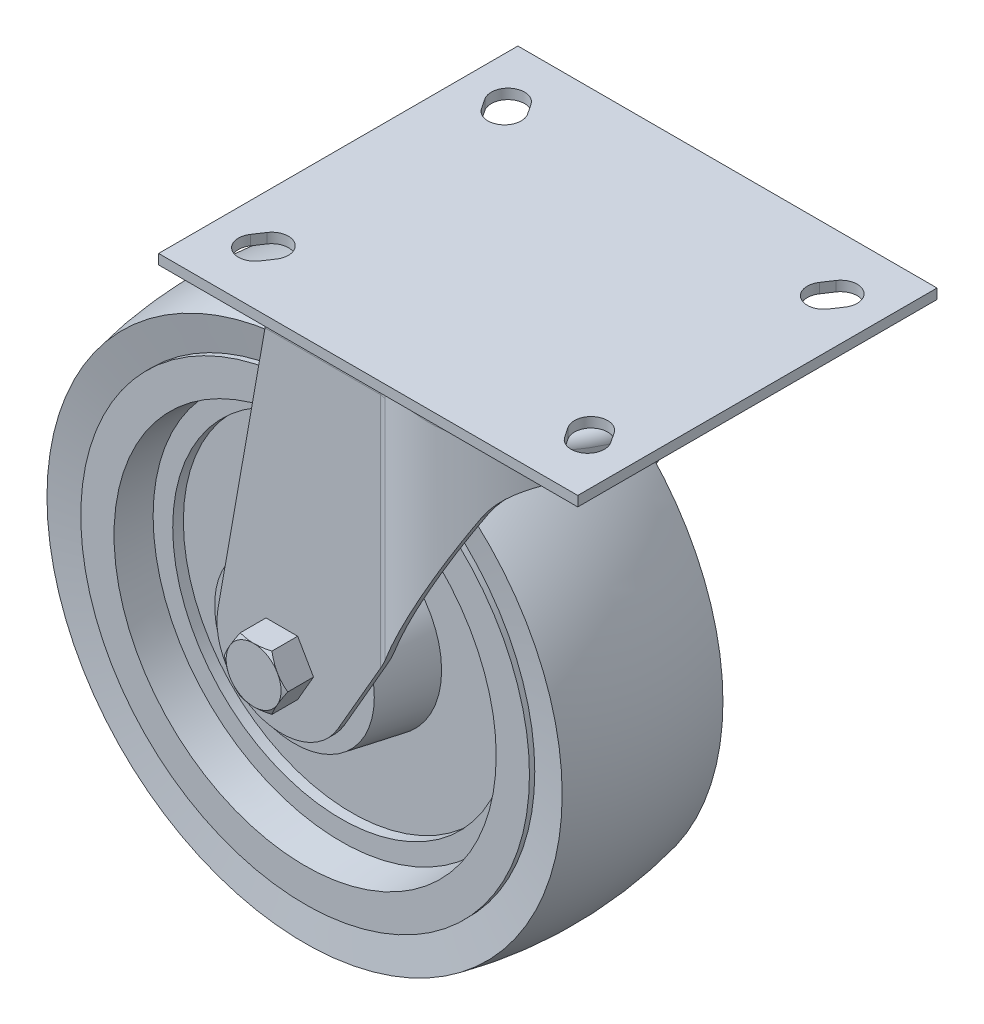
SolidWorks part; units mm, degrees
ref_plane "Front Plane" through (0, 0, 0) normal (0, 0, 1) x (1, 0, 0)
ref_plane "Top Plane" through (0, 0, 0) normal (0, 1, 0) x (1, 0, 0)
ref_plane "Right Plane" through (0, 0, 0) normal (1, 0, 0) x (0, 0, -1)
sketch "Sketch1" plane through (0, 0, 0) normal (0, 0, 1) x (1, 0, 0)
  line L0 (0, 0) -> (0, -150.8125)
  line L1 (-50.0062, 0) -> (50.0062, 0)
  line L2 (-50.0062, 0) -> (-50.0062, -2.3813)
  line L3 (-50.0062, -2.3813) -> (50.0062, -2.3813)
  line L4 (50.0062, 0) -> (50.0062, -2.3813)
  line L5 (0, -150.8125) -> (-38.862, -150.8125)
  line L6 (0, -12.3031) -> (-28.575, -12.3031)
  line L7 (-28.575, -12.3031) -> (-28.575, -10.3187)
  line L8 (-25.4, -7.1437) -> (0, -7.1438)
  line L9 (0, -7.1438) -> (0, -12.3031)
  line L10 (-25.4, -7.1437) -> (-24.5201, -5.6197)
  line L11 (-18.9109, -2.3813) -> (0, -2.3813)
  line L12 (-27.051, -12.3031) -> (-27.051, -13.8271)
  line L13 (-27.051, -13.8271) -> (0, -13.8271)
  line L14 (-25.4576, -95.0516) -> (10.6508, -32.51)
  line L15 (-35.0813, -80.7641) -> (-42.6427, -80.7641)
  line L16 (-42.6427, -80.7641) -> (-46.4235, -87.3125)
  line L17 (-46.4235, -87.3125) -> (-42.6427, -93.8609)
  line L18 (-42.6427, -93.8609) -> (-35.0813, -93.8609)
  line L19 (-35.0813, -93.8609) -> (-31.3005, -87.3125)
  line L20 (-31.3005, -87.3125) -> (-35.0813, -80.7641)
  line L21 (28.575, -22.1615) -> (0, -22.1615) construction
  line L22 (28.575, -22.1615) -> (28.575, -13.8271)
  line L23 (-38.862, -87.3125) -> (-38.862, -48.9313) construction
  line L24 (-54.105, -84.6248) -> (-42.3201, -17.7895)
  line L25 (-42.3201, -17.7895) -> (-28.575, -17.7895)
  line L26 (-28.575, -17.7895) -> (-28.575, -13.8271)
  circle A0 centre (-38.862, -87.3125) radius 63.5
  arc A1 (-28.575, -10.3187) -> (-25.4, -7.1437) centre (-25.4, -10.3187) cw
  arc A2 (-24.5201, -5.6197) -> (-18.9109, -2.3813) centre (-18.9109, -8.8582) cw
  circle A3 centre (-38.862, -87.3125) radius 15.4781
  circle A4 centre (-38.862, -87.3125) radius 6.5484 construction
  arc A5 (10.6508, -32.51) -> (28.575, -22.1615) centre (28.575, -42.8586) cw
  dimension "Wheel Dia" = 127
  dimension "D14" = 13.0969
  dimension "D15" = 30.9562
  dimension "Height" = 150.8125
  dimension "Plate Length" = 100.0125
  dimension "Plate Thickness" = 2.3813
  dimension "Swivel Radius" = 102.362
  dimension "D6" = 5.1594
  dimension "D7" = 3.175
  dimension "D8" = 28.575
  dimension "D9" = 4.7625
  dimension "D10" = 60
  dimension "D11" = 1.524
  dimension "D12" = 1.524
  dimension "D13" = 1.524
  dimension "D16" = 8.3344
  dimension "D17" = 28.575
  dimension "D18" = 30
  dimension "D19" = 10
  dimension "D20" = 3.9624
sketch "Sketch2" plane through (0, 0, 0) normal (0, 0, 1) x (1, 0, 0)
  line L1 (-50.0062, -2.3813) -> (50.0062, -2.3813)
  line L2 (-50.0062, -2.3813) -> (-50.0062, 0)
  line L3 (-50.0062, 0) -> (50.0062, 0)
  line L4 (50.0062, -2.3813) -> (50.0062, 0)
extrude "Boss-Extrude1" add sketch "Sketch2" along normal mid plane 85.725
sketch "Sketch3" plane through (0, 0, 0) normal (0, 1, 0) x (1, 0, 0)
  line L0 (38.1, 27.7812) -> (39.6875, 30.1625) construction
  line L1 (34.7978, 29.9827) -> (36.3853, 32.364)
  line L2 (41.4022, 25.5798) -> (42.9897, 27.961)
  line L3 (0, 0) -> (0, 42.8625) construction
  line L4 (50.0062, 42.8625) -> (-50.0062, 42.8625) construction
  line L5 (0, 0) -> (50.0062, 0) construction
  line L6 (-50.0062, 0) -> (50.0062, 0) construction
  line L7 (-38.1, 27.7812) -> (-39.6875, 30.1625) construction
  line L8 (-34.7978, 29.9827) -> (-36.3853, 32.364)
  line L9 (-41.4022, 25.5798) -> (-42.9897, 27.961)
  line L10 (-38.1, -27.7812) -> (-39.6875, -30.1625) construction
  line L11 (-34.7978, -29.9827) -> (-36.3853, -32.364)
  line L12 (-41.4022, -25.5798) -> (-42.9897, -27.961)
  line L13 (38.1, -27.7812) -> (39.6875, -30.1625) construction
  line L14 (34.7978, -29.9827) -> (36.3853, -32.364)
  line L15 (41.4022, -25.5798) -> (42.9897, -27.961)
  arc A0 (34.7978, 29.9827) -> (41.4022, 25.5798) centre (38.1, 27.7812) ccw
  arc A1 (42.9897, 27.961) -> (36.3853, 32.364) centre (39.6875, 30.1625) ccw
  arc A2 (-34.7978, 29.9827) -> (-41.4022, 25.5798) centre (-38.1, 27.7812) cw
  arc A3 (-42.9897, 27.961) -> (-36.3853, 32.364) centre (-39.6875, 30.1625) cw
  arc A4 (-34.7978, -29.9827) -> (-41.4022, -25.5798) centre (-38.1, -27.7812) ccw
  arc A5 (-42.9897, -27.961) -> (-36.3853, -32.364) centre (-39.6875, -30.1625) ccw
  arc A6 (34.7978, -29.9827) -> (41.4022, -25.5798) centre (38.1, -27.7812) cw
  arc A7 (42.9897, -27.961) -> (36.3853, -32.364) centre (39.6875, -30.1625) cw
  point P2 (38.8938, 28.9719)
  point P17 (-38.8938, 28.9719)
  point P24 (-38.8938, -28.9719)
  point P31 (38.8938, -28.9719)
  dimension "D2" = 76.2
  dimension "D3" = 79.375
  dimension "D5" = 60.325
  dimension "D1" = 7.9375
  dimension "D4" = 55.5625
extrude "Cut-Extrude1" cut sketch "Sketch3" against normal blind 85.725
ref_plane "Plane1" through (-38.862, 0, 0) normal (1, 0, 0) x (0, 0, -1)
sketch "Sketch4" plane through (-38.862, 0, 0) normal (1, 0, 0) x (0, 0, -1)
  line L1 (19.05, -23.8125) -> (-19.05, -23.8125) construction
  line L2 (19.05, -23.8125) -> (19.05, -87.3125) construction
  line L3 (19.05, -87.3125) -> (-19.05, -87.3125) construction
  line L4 (-19.05, -23.8125) -> (-19.05, -87.3125) construction
  line L5 (0, -23.8125) -> (0, -150.8125) construction
  line L6 (-21.59, -87.3125) -> (-21.59, -68.2625)
  line L7 (-21.59, -68.2625) -> (-7.9375, -65.8552)
  line L8 (-7.9375, -65.8552) -> (-7.9375, -47.1466)
  line L9 (-7.9375, -47.1466) -> (-10.4775, -47.1466)
  line L10 (-10.4775, -47.1466) -> (-10.4775, -42.4695)
  line L11 (-10.4775, -42.4695) -> (-19.05, -41.7195)
  line L12 (-19.05, -41.7195) -> (-19.05, -33.782)
  line L13 (-19.05, -33.782) -> (-17.78, -33.782)
  line L14 (-17.78, -33.782) -> (-19.1796, -25.8445)
  line L15 (0, 0) -> (0, -150.8125) construction
  line L16 (0, -23.8125) -> (0, -115.3445) construction
  line L17 (17.78, -33.782) -> (19.1796, -25.8445)
  line L18 (19.05, -33.782) -> (17.78, -33.782)
  line L19 (19.05, -41.7195) -> (19.05, -33.782)
  line L20 (10.4775, -42.4695) -> (19.05, -41.7195)
  line L21 (10.4775, -47.1466) -> (10.4775, -42.4695)
  line L22 (7.9375, -47.1466) -> (10.4775, -47.1466)
  line L23 (7.9375, -65.8552) -> (7.9375, -47.1466)
  line L24 (21.59, -68.2625) -> (7.9375, -65.8552)
  line L25 (21.59, -68.2625) -> (21.59, -87.3125)
  line L26 (-21.59, -87.3125) -> (21.59, -87.3125)
  arc A0 (-19.1796, -25.8445) -> (19.1796, -25.8445) centre (0, -115.3445) cw
  point P7 (0, -23.8125)
  dimension "Wheel Width" = 38.1
  dimension "D2" = 2.54
  dimension "D3" = 15.875
  dimension "D4" = 7.9375
  dimension "D5" = 1.27
  dimension "D6" = 10
  dimension "D7" = 2.54
  dimension "D8" = 38.1
  dimension "D9" = 10
  dimension "D10" = 5
  dimension "D11" = 7.9375
  dimension "D12" = 2.032
  dimension "D13" = 23.3857
  dimension "D14" = 4.6771
revolve "Revolve1" add sketch "Sketch4" angle 360 about L26
sketch "Sketch5" plane through (0, 0, 0) normal (0, 0, 1) x (1, 0, 0)
  line L0 (-27.051, -13.8271) -> (0, -13.8271) construction
  line L1 (0, -12.3031) -> (-28.575, -12.3031) construction
  line L2 (-27.051, -13.8271) -> (0, -13.8271)
  line L3 (-27.051, -12.3031) -> (-28.575, -12.3031)
  line L4 (-25.4, -7.1437) -> (-24.5201, -5.6197) construction
  line L5 (-25.4, -7.1437) -> (-24.5201, -5.6197)
  line L6 (-28.575, -10.3187) -> (-28.575, -12.3031)
  line L7 (-27.051, -13.8271) -> (-27.051, -12.3031)
  line L8 (0, -13.8271) -> (0, -2.3813)
  line L9 (0, -2.3813) -> (-18.9109, -2.3813)
  arc A0 (-25.4, -7.1437) -> (-28.575, -10.3187) centre (-25.4, -10.3187) ccw construction
  arc A1 (-18.9109, -2.3813) -> (-24.5201, -5.6197) centre (-18.9109, -8.8582) ccw construction
  arc A2 (-25.4, -7.1437) -> (-28.575, -10.3187) centre (-25.4, -10.3187) ccw
  arc A3 (-18.9109, -2.3813) -> (-24.5201, -5.6197) centre (-18.9109, -8.8582) ccw
revolve "Revolve2" add sketch "Sketch5" angle 360 about L8
sketch "Sketch6" plane through (0, -13.8271, 0) normal (0, -1, 0) x (1, 0, 0)
  circle A0 centre (0, 0) radius 28.575
extrude "Boss-Extrude2" add sketch "Sketch6" along normal up to vertex (136.9854 mm away) separate body up to point (0, -150.8125, 0)
sketch "Sketch7" plane through (0, 0, 0) normal (0, 0, 1) x (1, 0, 0)
  line L0 (-42.3201, -17.7895) -> (-28.575, -17.7895) construction
  line L1 (-60.455, -17.7895) -> (0, -17.7895)
  line L2 (-60.455, -17.7895) -> (-60.455, -150.8125)
  line L3 (-60.455, -150.8125) -> (0, -150.8125)
  line L4 (0, -17.7895) -> (0, -150.8125)
  dimension "D1" = 6.35
extrude "Boss-Extrude3" add sketch "Sketch7" along normal mid plane 49.2125 separate body
fillet "Fillet1" radius 3.175 2 edges at (-30.2275, -17.7895, 24.6063) (-30.2275, -17.7895, -24.6063)
fillet "Fillet2" radius 3.175 1 edges at (28.575, -13.8271, 0)
combine bodies "Combine1" operation type add bodies to combine 105 106
fillet "Fillet3" radius 3.175 5 edges at (-14.528, -85.8885, -24.6063) (-14.8682, -19.8447, -24.4022) (-28.575, -17.7895, 0) (-15.5609, -19.0531, 23.9664) (-14.528, -85.8885, 24.6063)
shell "Shell1" thickness 1.5875
sketch "Sketch8" plane through (0, 0, 0) normal (0, 0, 1) x (1, 0, 0)
  line L0 (-54.105, -84.6248) -> (-42.3201, -17.7895) construction
  line L1 (-25.4576, -95.0516) -> (10.6508, -32.51) construction
  line L2 (-54.105, -84.6248) -> (-42.3201, -17.7895)
  line L3 (-25.4576, -95.0516) -> (10.6508, -32.51)
  circle A0 centre (-38.862, -87.3125) radius 15.4781 construction
  arc A1 (28.575, -22.1615) -> (10.6508, -32.51) centre (28.575, -42.8586) ccw construction
  arc A2 (-54.105, -84.6248) -> (-25.4576, -95.0516) centre (-38.862, -87.3125) ccw
  arc A3 (28.575, -22.1615) -> (10.6508, -32.51) centre (28.575, -42.8586) ccw
extrude "Cut-Extrude2" cut sketch "Sketch8" against normal through all and the other way through all flip side to cut
sketch "Sketch9" plane through (0, 0, 0) normal (0, 0, 1) x (1, 0, 0)
  circle A0 centre (-38.862, -87.3125) radius 4.7625
  dimension "D1" = 9.525
extrude "Boss-Extrude4" add sketch "Sketch9" along normal up to surface (24.6062 mm away) separate body up to face at (-31.5118, -62.2411, 24.6063)
sketch "Sketch10" plane through (0, 0, 24.6063) normal (0, 0, 1) x (1, 0, 0)
  line L0 (-42.6427, -80.7641) -> (-46.4235, -87.3125) construction
  line L1 (-46.4235, -87.3125) -> (-42.6427, -93.8609) construction
  line L2 (-42.6427, -93.8609) -> (-35.0813, -93.8609) construction
  line L3 (-35.0813, -93.8609) -> (-31.3005, -87.3125) construction
  line L4 (-31.3005, -87.3125) -> (-35.0813, -80.7641) construction
  line L5 (-35.0813, -80.7641) -> (-42.6427, -80.7641) construction
  line L6 (-42.6427, -80.7641) -> (-46.4235, -87.3125)
  line L7 (-46.4235, -87.3125) -> (-42.6427, -93.8609)
  line L8 (-42.6427, -93.8609) -> (-35.0813, -93.8609)
  line L9 (-35.0813, -93.8609) -> (-31.3005, -87.3125)
  line L10 (-31.3005, -87.3125) -> (-35.0813, -80.7641)
  line L11 (-35.0813, -80.7641) -> (-42.6427, -80.7641)
extrude "Boss-Extrude5" add sketch "Sketch10" along normal blind 6.731
sketch "Sketch11" plane through (0, 0, 31.3373) normal (0, 0, 1) x (1, 0, 0)
  circle A0 centre (-38.862, -87.3125) radius 6.5484 construction
  circle A1 centre (-38.862, -87.3125) radius 6.5484
extrude "Cut-Extrude3" cut sketch "Sketch11" against normal through all draft 60 flip side to cut
mirror "Mirror1" about plane through (0, 0, 0) normal (0, 0, 1) of bodies 111
combine bodies "Combine2" operation type add bodies to combine 108 104
combine bodies "Combine3" operation type add bodies to combine 113 112
equation "\"D14@Sketch4\" = \"D13@Sketch4\"/5"
equation "\"D1@Boss-Extrude3\" = \"Wheel Width@Sketch4\"+(\"Leg Thickness@Shell1\"*2)+.3125"
equation "\"D1@Fillet1\" = \"Leg Thickness@Shell1\"*2"
equation "\"D1@Fillet2\" = \"D1@Fillet1\""
equation "\"D1@Fillet3\" = \"D1@Fillet1\""
equation "\"D17@Sketch1\" = \"D8@Sketch1\""
